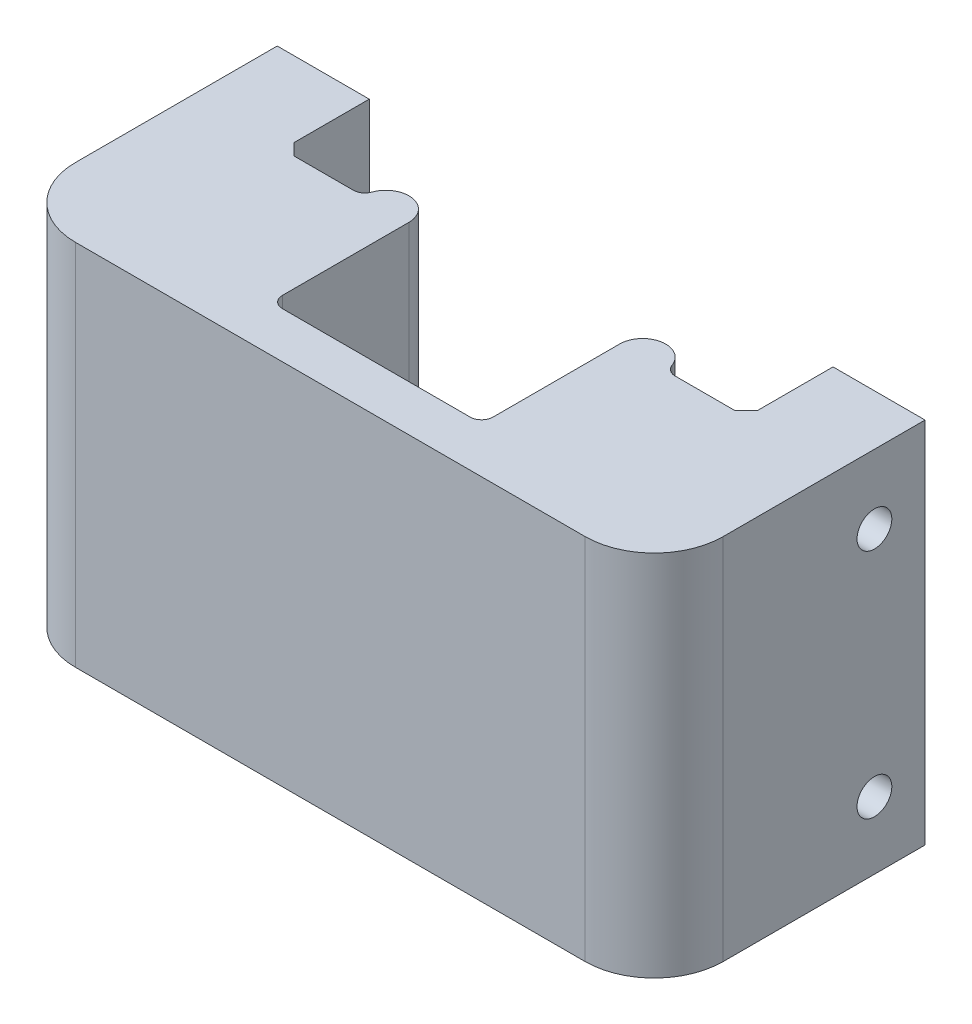
SolidWorks part; units mm, degrees
material "Polycarbonate"
ref_plane "Front Plane" through (0, 0, 0) normal (0, 0, 1) x (1, 0, 0)
ref_plane "Top Plane" through (0, 0, 0) normal (0, 1, 0) x (1, 0, 0)
ref_plane "Right Plane" through (0, 0, 0) normal (1, 0, 0) x (0, 0, -1)
sketch "Sketch1" plane through (0, 0, 0) normal (0, 1, 0) x (1, 0, 0)
  line L0 (0, 0) -> (0, 5.9944)
  line L1 (0, 5.9944) -> (-6.35, 5.9944)
  line L2 (-6.35, 5.9944) -> (-6.35, -12.7)
  line L3 (-6.35, -12.7) -> (38.354, -12.7)
  line L4 (8.7312, -8.7312) -> (8.7312, 1.5875)
  line L5 (5.5562, 0) -> (0, 0)
  line L6 (5.5562, 0) -> (5.5562, 1.5875)
  line L7 (5.5562, 1.5875) -> (8.7312, 1.5875)
  line L9 (23.2728, -8.7312) -> (23.2728, 1.5875)
  line L10 (9.525, -9.525) -> (22.479, -9.525)
  line L12 (16.002, -9.525) -> (16.002, -12.7) construction
  line L13 (26.4477, 1.5875) -> (23.2728, 1.5875)
  line L14 (26.4477, 0) -> (26.4477, 1.5875)
  line L15 (26.4477, 0) -> (32.004, 0)
  line L16 (32.004, 0) -> (32.004, 5.9944)
  line L17 (32.004, 5.9944) -> (38.354, 5.9944)
  line L18 (38.354, 5.9944) -> (38.354, -12.7)
  arc A0 (9.525, -9.525) -> (8.7312, -8.7312) centre (9.525, -8.7312) cw
  arc A1 (22.479, -9.525) -> (23.2728, -8.7312) centre (22.479, -8.7312) ccw
  point P10 (5.5562, 0.7937)
  point P18 (8.7312, -9.525)
  dimension "D8" = 0.7937
  dimension "D1" = 5.9944
  dimension "D2" = 14.2875
  dimension "D3" = 16.002
  dimension "D4" = 6.35
  dimension "D5" = 5.5562
  dimension "D6" = 15.0812
  dimension "D7" = 1.5875
  dimension "D9" = 3.175
extrude "Boss-Extrude1" add sketch "Sketch1" along normal blind 25.4 contours L7 L6 L5 L0 L1 L2 L3 L4 | L18 L17 L16 L15 L14 L13 L9 L3 region at (2.7781, 0, 0.4846)
chamfer "Chamfer1" distance 0.7937 angle 45 2 edges at (0, 12.7, 0) (32.004, 12.7, 0)
hole_wizard "M2 Clearance Hole1" positions "Sketch3" profile "Sketch4" hole size "M2" standard "ANSI Metric" end condition up to next
sketch "Sketch3" plane through (0, 0, 0) normal (1, 0, 0) x (0, 0, -1)
  line L0 (2.5, 20.6391) -> (2.5, 4.6391) construction
  line L2 (5.9944, 25.4) -> (5.9944, 0) construction
  line L3 (5.9944, 25.4) -> (-12.7, 25.4) construction
  point P0 (2.5, 20.6391)
  point P3 (2.5, 4.6391)
  dimension "D1" = 16
  dimension "D2" = 4.7609
  dimension "D3" = 3.4944
sketch "Sketch4" plane through (0, 20.6391, -2.5) normal (0, 1, 0) x (0, 0, -1)
  line L0 (0, 0) -> (0, 6.35)
  line L1 (0, 6.35) -> (1.2, 6.35)
  line L2 (1.2, 6.35) -> (1.2, 0)
  line L5 (1.2, 0) -> (0, 0)
  line L11 (0, -6.35) -> (0, 107.95) construction
  dimension "Thru Hole Dia." = 2.4
  dimension "Thru Hole Depth" = 6.35
fillet "Fillet1" radius 4.7625 2 edges at (-6.35, 12.7, 12.7) (38.354, 12.7, 12.7)
fillet "Fillet5" 2 edges at (5.5562, 12.7, -1.5875) (8.7312, 12.7, -1.5875) type full round first side face at (5.5562, 12.7, -0.7937) second side face at (8.7312, 12.7, 3.5719) middle face at (7.1437, 12.7, -1.5875)
fillet "Fillet6" 2 edges at (26.4477, 12.7, -1.5875) (23.2728, 12.7, -1.5875) type full round first side face at (26.4477, 12.7, -0.7937) second side face at (23.2728, 12.7, 3.5719) middle face at (24.8603, 12.7, -1.5875)
fillet "Fillet7" radius 0.7937 2 edges at (5.5562, 12.7, 0) (26.4477, 12.7, 0)
hole_wizard "M2 Clearance Hole2" positions "Sketch5" profile "Sketch6" hole size "M2" standard "ANSI Metric" end condition through all
sketch "Sketch5" plane through (32.004, 0, 0) normal (-1, 0, 0) x (0, 0, 1)
  line L0 (-5.9944, 25.4) -> (-5.9944, 0) construction
  line L1 (-5.9944, 25.4) -> (7.9375, 25.4) construction
  point P0 (-2.5, 4.6391)
  point P3 (-2.5, 20.6391)
  dimension "D1" = 16
  dimension "D2" = 3.4944
  dimension "D3" = 4.7609
sketch "Sketch6" plane through (32.004, 4.6391, -2.5) normal (0, 1, 0) x (0, 0, 1)
  line L0 (0, 0) -> (0, 6.35)
  line L1 (0, 6.35) -> (1.2, 6.35)
  line L2 (1.2, 6.35) -> (1.2, 0)
  line L5 (1.2, 0) -> (0, 0)
  line L11 (0, -6.35) -> (0, 107.95) construction
  dimension "Thru Hole Dia." = 2.4
  dimension "Thru Hole Depth" = 6.35
